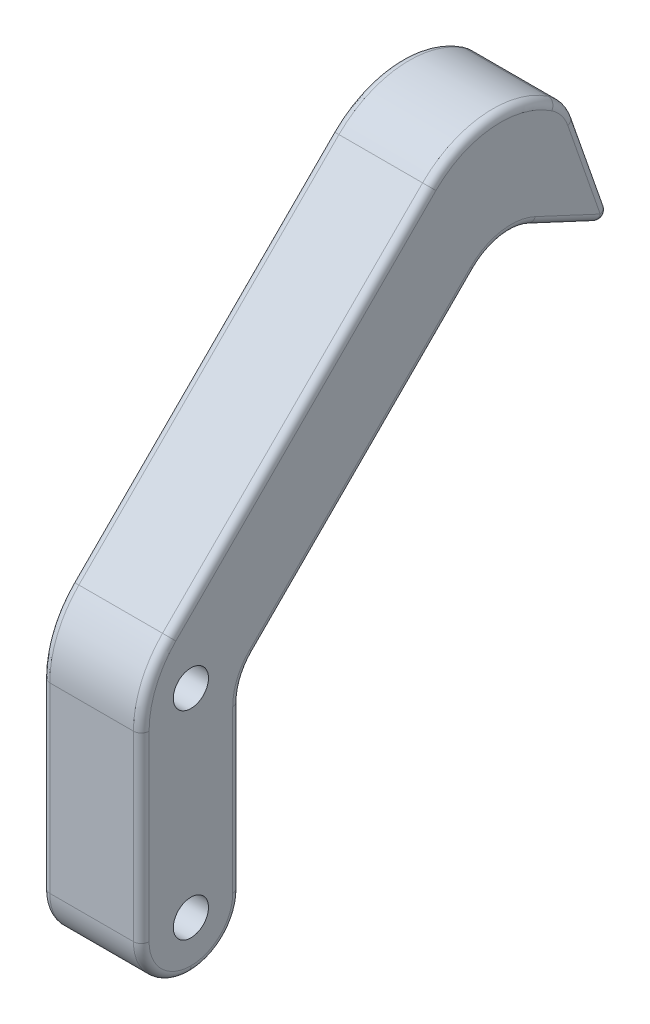
SolidWorks part; units mm, degrees
ref_plane "Front Plane" through (0, 0, 0) normal (0, 0, 1) x (1, 0, 0)
ref_plane "Top Plane" through (0, 0, 0) normal (0, 1, 0) x (1, 0, 0)
ref_plane "Right Plane" through (0, 0, 0) normal (1, 0, 0) x (0, 0, -1)
sketch "Sketch1" plane through (0, 0, 0) normal (1, 0, 0) x (0, 0, -1)
  line L0 (-6.35, 3.175) -> (-6.35, -31.75)
  line L1 (-6.35, -31.75) -> (6.35, -31.75)
  line L2 (6.35, -31.75) -> (6.35, -2.0855)
  line L3 (6.35, -2.0855) -> (48.5922, 40.1567)
  line L4 (48.5922, 40.1567) -> (39.6119, 49.1369)
  line L5 (39.6119, 49.1369) -> (-6.35, 3.175)
  line L6 (48.5922, 40.1567) -> (54.079, 24.4303)
  line L8 (54.079, 24.4303) -> (39.6119, 31.1764)
  circle A0 centre (0, 0) radius 2.25
  circle A2 centre (0, -25.4) radius 2.25
  point P5 (0, 0)
  point P12 (48.5584, 22.1573)
  point P15 (0, 0)
  dimension "D2" = 4.5
  dimension "D1" = 25.4
  dimension "D3" = 135
  dimension "D4" = 12.7
  dimension "D5" = 6.35
  dimension "D6" = 3.175
  dimension "D7" = 6.35
  dimension "D8" = 65
  dimension "D9" = 110
  dimension "D10" = 12.7
  dimension "D11" = 15
extrude "Boss-Extrude1" add sketch "Sketch1" along normal blind 12.7 contours L4 L5 L0 L1 L2 L3 A2 A0 | L8 L6 L3 region at (0, 10.2159, -14.8112) region at (0, 31.9211, -47.4277)
fillet "Fillet1" radius 12.7 2 edges at (6.35, 3.175, 6.35) (6.35, 49.1369, -39.6119)
fillet "Fillet2" radius 6.35 5 edges at (6.35, 40.1567, -48.5922) (6.35, 31.1764, -39.6119) (6.35, -31.75, 6.35) (6.35, -31.75, -6.35) (6.35, -2.0855, -6.35)
fillet "Fillet3" radius 1 27 edges at (0, 31.4813, -51.619) (0, 40.3161, -48.1935) (0, 43.818, -38.3954) (0, 23.5257, -14.0007) (0, 2.7746, 5.3833) (0, -13.7428, 6.35) (0, -29.8901, 4.4901) (0, -29.8901, -4.4901) (0, -15.0579, -6.35) (0, -2.2857, -6.8334) (0, 26.8638, -48.8604) (0, 29.7958, -39.8554) (12.7, 31.4813, -51.619) (12.7, 40.3161, -48.1935) (12.7, 43.818, -38.3954) (12.7, 23.5257, -14.0007) (12.7, 2.7746, 5.3833) (12.7, -13.7428, 6.35) (12.7, -29.8901, 4.4901) (12.7, -29.8901, -4.4901) (12.7, -15.0579, -6.35) (12.7, -2.2857, -6.8334) (12.7, 26.8638, -48.8604) (12.7, 29.7958, -39.8554) (0, 13.9034, -22.3389) (12.7, 13.9034, -22.3389) (6.35, 24.4303, -54.079)
